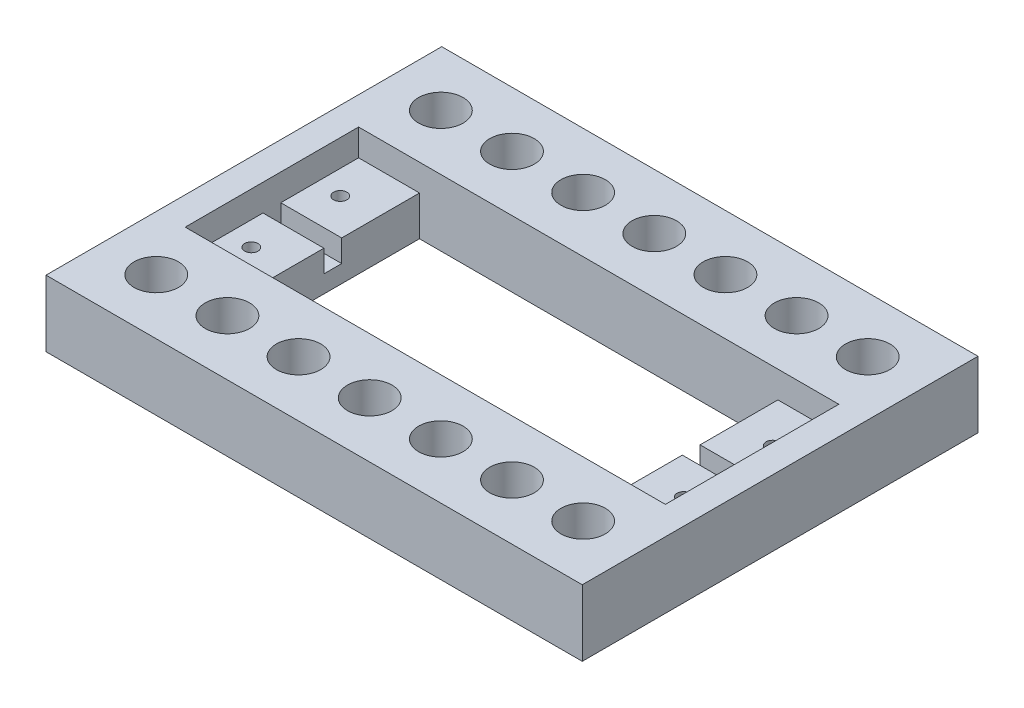
SolidWorks part; units mm, degrees
ref_plane "Front Plane" through (0, 0, 0) normal (0, 0, 1) x (1, 0, 0)
ref_plane "Top Plane" through (0, 0, 0) normal (0, 1, 0) x (1, 0, 0)
ref_plane "Right Plane" through (0, 0, 0) normal (1, 0, 0) x (0, 0, -1)
sketch "Sketch1" plane through (0, 0, 0) normal (0, 1, 0) x (1, 0, 0)
  line L0 (-34.3973, 0) -> (32.9918, 0) construction
  line L1 (-20.15, 9.75) -> (20.15, 9.75)
  line L2 (-20.15, 9.75) -> (-20.15, -9.75)
  line L3 (-20.15, -9.75) -> (20.15, -9.75)
  line L4 (20.15, 9.75) -> (20.15, -9.75)
  line L5 (-20.15, 9.75) -> (20.15, -9.75) construction
  line L6 (-20.15, -9.75) -> (20.15, 9.75) construction
  line L7 (0, 26.5192) -> (0, -28.2205) construction
  line L9 (-30.15, 22.25) -> (30.15, 22.25)
  line L10 (-30.15, 22.25) -> (-30.15, -22.25)
  line L11 (-30.15, -22.25) -> (30.15, -22.25)
  line L12 (30.15, 22.25) -> (30.15, -22.25)
  line L13 (-27, 9.75) -> (27, 9.75) construction
  line L14 (-27, 9.75) -> (-27, -9.75) construction
  line L15 (-27, -9.75) -> (27, -9.75) construction
  line L16 (27, 9.75) -> (27, -9.75) construction
  line L17 (-27, 9.75) -> (27, -9.75) construction
  line L18 (-27, -9.75) -> (27, 9.75) construction
  circle A0 centre (-24.315, -5) radius 0.75
  circle A1 centre (-24.315, 5) radius 0.75
  circle A2 centre (24.315, -5) radius 0.75
  circle A3 centre (24.315, 5) radius 0.75
  point P0 (0, 0)
  point P14 (0, 0)
  dimension "D9" = 24.315
  dimension "D8" = 1.5
  dimension "D10" = 5
  dimension "D1" = 40.3
  dimension "D2" = 19.5
  dimension "D3" = 12.5
  dimension "D4" = 12.5
  dimension "D5" = 10
  dimension "D6" = 10
  dimension "D7" = 54
extrude "Boss-Extrude1" add sketch "Sketch1" along normal blind 7.46
sketch "Sketch3" plane through (0, 7.46, 0) normal (0, 1, 0) x (1, 0, 0)
  line L1 (-27, 9.75) -> (27, 9.75)
  line L2 (-27, 9.75) -> (-27, -9.75)
  line L3 (-27, -9.75) -> (27, -9.75)
  line L4 (27, 9.75) -> (27, -9.75)
  line L5 (-27, 9.75) -> (27, -9.75) construction
  line L6 (-27, -9.75) -> (27, 9.75) construction
  point P0 (0, 0)
  dimension "D1" = 19.5
  dimension "D2" = 54
extrude "Cut-Extrude1" cut sketch "Sketch3" against normal blind 3
sketch "Sketch4" plane through (0, 7.46, 0) normal (0, 1, 0) x (1, 0, 0)
  line L0 (0, 22.25) -> (0, 9.75) construction
  line L1 (30.15, 22.25) -> (-30.15, 22.25) construction
  line L2 (27, 9.75) -> (-27, 9.75) construction
  line L3 (0, 16) -> (-30.15, 16) construction
  line L4 (-30.15, 22.25) -> (-30.15, -22.25) construction
  line L5 (-20.15, 0) -> (20.15, 0) construction
  line L6 (-20.15, 9.75) -> (-20.15, -9.75) construction
  line L7 (20.15, -9.75) -> (20.15, 9.75) construction
  circle A0 centre (0, 16) radius 2.5
  circle A1 centre (8, 16) radius 2.5
  circle A2 centre (16, 16) radius 2.5
  circle A3 centre (24, 16) radius 2.5
  circle A4 centre (-24, 16) radius 2.5
  circle A5 centre (-16, 16) radius 2.5
  circle A6 centre (-8, 16) radius 2.5
  circle A7 centre (24, -16) radius 2.5
  circle A8 centre (16, -16) radius 2.5
  circle A9 centre (8, -16) radius 2.5
  circle A10 centre (0, -16) radius 2.5
  circle A11 centre (-8, -16) radius 2.5
  circle A12 centre (-16, -16) radius 2.5
  circle A13 centre (-24, -16) radius 2.5
  dimension "D1" = 5
  dimension "D3" = 8
  dimension "D2" = 4
extrude "Cut-Extrude2" cut sketch "Sketch4" against normal through all
sketch "Sketch5" plane through (0, 4.46, 0) normal (0, 1, 0) x (1, 0, 0)
  line L0 (-27, 0) -> (27, 0) construction
  line L1 (-27, 9.75) -> (-27, -9.75) construction
  line L2 (27, -9.75) -> (27, 9.75) construction
  line L3 (-27, -1) -> (-20.15, -1)
  line L4 (-20.15, 9.75) -> (-20.15, -9.75) construction
  line L5 (-27, 1) -> (-20.15, 1)
  line L6 (-27, -1) -> (-27, 1)
  line L7 (-20.15, -1) -> (-20.15, 1)
  line L8 (0, 0) -> (0, -25.0299) construction
  line L9 (20.15, -1) -> (20.15, 1)
  line L10 (27, 1) -> (20.15, 1)
  line L11 (27, -1) -> (20.15, -1)
  line L12 (27, -1) -> (27, 1)
  dimension "D1" = 2
extrude "Cut-Extrude3" cut sketch "Sketch5" against normal blind 2.5
